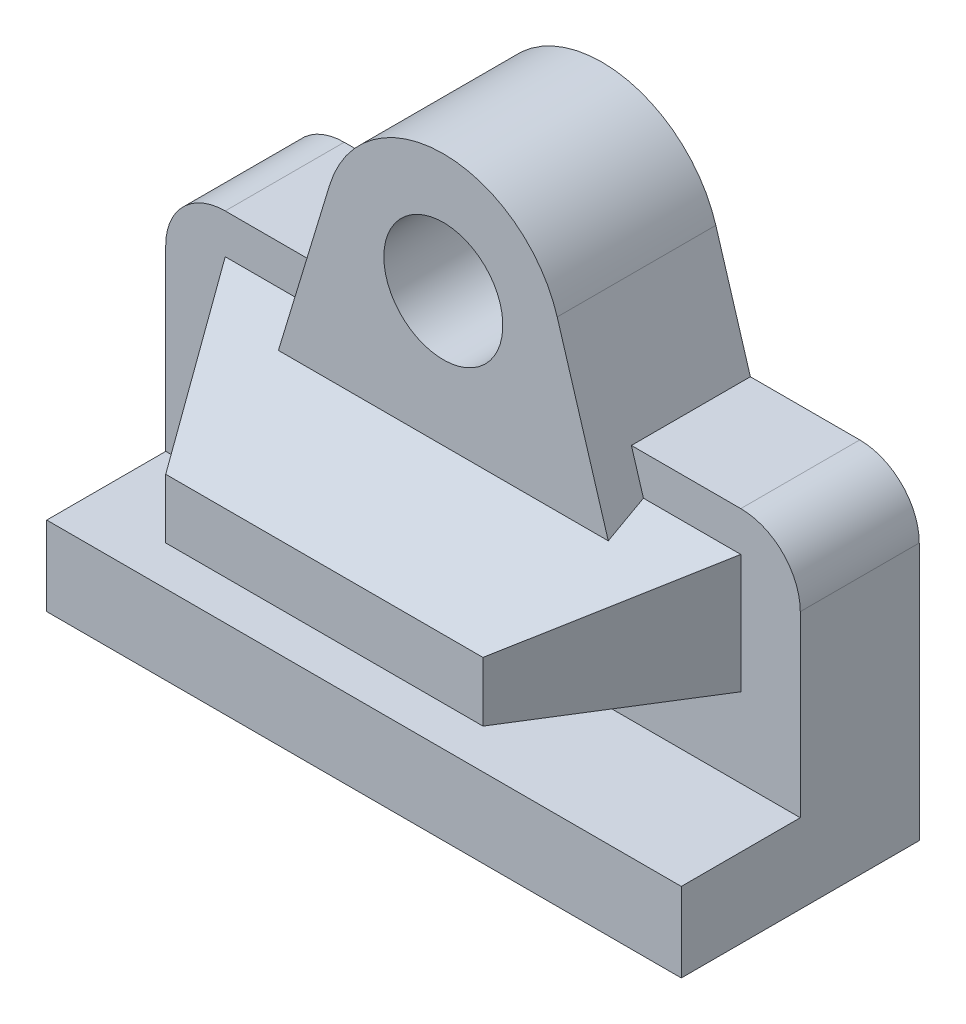
SolidWorks part; units mm, degrees
ref_plane "Front Plane" through (0, 0, 0) normal (0, 0, 1) x (1, 0, 0)
ref_plane "Top Plane" through (0, 0, 0) normal (0, 1, 0) x (1, 0, 0)
ref_plane "Right Plane" through (0, 0, 0) normal (1, 0, 0) x (0, 0, -1)
sketch "Sketch1" plane through (0, 0, 0) normal (0, 0, 1) x (1, 0, 0)
  line L0 (0, 0) -> (0, 63.5) construction
  line L1 (-50.8, 0) -> (50.8, 0)
  line L2 (50.8, 0) -> (50.8, 12.7)
  line L3 (50.8, 12.7) -> (-50.8, 12.7)
  line L4 (50.8, 12.7) -> (50.8, 41.275)
  line L5 (41.275, 50.8) -> (23.7595, 50.8)
  line L6 (-50.8, 25.4) -> (50.8, 25.4) construction
  line L7 (18.2298, 69.0298) -> (28.575, 34.925)
  line L8 (28.575, 34.925) -> (-28.575, 34.925)
  line L9 (0, 63.5) -> (0, 73.025) construction
  line L10 (-50.8, 0) -> (-50.8, 12.7)
  line L11 (-18.2298, 69.0298) -> (-28.575, 34.925)
  line L12 (-41.275, 50.8) -> (-23.7595, 50.8)
  line L13 (-50.8, 12.7) -> (-50.8, 41.275)
  arc A0 (50.8, 41.275) -> (41.275, 50.8) centre (41.275, 41.275) ccw
  circle A1 centre (0, 63.5) radius 9.525
  arc A2 (-50.8, 41.275) -> (-41.275, 50.8) centre (-41.275, 41.275) cw
  circle A3 centre (0, 63.5) radius 19.05
  point P6 (-50.8, 50.8)
  point P10 (50.8, 50.8)
  point P21 (0, 25.4)
  point P25 (0, 34.925)
  point P27 (0, 12.7)
  dimension "D4" = 9.525
  dimension "D5" = 19.05
  dimension "D10" = 38.1
  dimension "D1" = 50.8
  dimension "D2" = 12.7
  dimension "D3" = 38.1
  dimension "D6" = 12.7
  dimension "D7" = 38.1
  dimension "D8" = 28.575
  dimension "D9" = 34.925
extrude "Boss-Extrude1" add sketch "Sketch1" along normal blind 19.05 contours A3 A1 | A3 L11 L8 L7 | A2 L13 L3 L4 A0 L5 L7 L8 L11 L12 region at (0, 28.5216, 0) region at (0, 43.5132, 0) region at (0, 82.0112, 0)
extrude "Boss-Extrude2" add sketch "Sketch1<3>" along normal blind 25.4 contours A3 L11 L8 L7 | A3 A1 region at (0, 43.5132, 0) region at (0, 82.0112, 0)
sketch "Sketch1<3>" plane through (0, 0, 0) normal (0, 0, 1) x (1, 0, 0) same geometry as "Sketch1"
extrude "Boss-Extrude3" add sketch "Sketch1<4>" along normal blind 38.1 contours L10 L1 L2 L3 region at (0, 6.35, 0)
sketch "Sketch1<4>" plane through (0, 0, 0) normal (0, 0, 1) x (1, 0, 0) same geometry as "Sketch1"
sketch "Sketch2" plane through (0, 0, 19.05) normal (0, 0, 1) x (1, 0, 0)
  line L0 (0, 12.7) -> (0, 53.975) construction
  line L1 (50.8, 12.7) -> (-50.8, 12.7) construction
  line L2 (-41.275, 44.45) -> (41.275, 44.45)
  line L3 (50.8, 12.7) -> (-50.8, 12.7) construction
  line L4 (-41.275, 44.45) -> (-41.275, 25.4)
  line L5 (-41.275, 25.4) -> (41.275, 25.4)
  line L6 (41.275, 25.4) -> (41.275, 44.45)
  circle A0 centre (0, 63.5) radius 9.525 construction
  point P9 (0, 44.45)
  dimension "D1" = 31.75
  dimension "D2" = 19.05
  dimension "D3" = 82.55
ref_plane "Plane1" through (0, 0, 44.45) normal (0, 0, 1) x (1, 0, 0)
sketch "Sketch3" plane through (0, 0, 44.45) normal (0, 0, 1) x (1, 0, 0)
  line L0 (-41.275, 25.4) -> (41.275, 25.4) construction
  line L1 (-25.4, 25.4) -> (25.4, 25.4)
  line L2 (-25.4, 25.4) -> (-25.4, 34.925)
  line L3 (-25.4, 34.925) -> (25.4, 34.925)
  line L4 (25.4, 25.4) -> (25.4, 34.925)
  line L5 (0, 12.7) -> (0, 53.975) construction
  point P8 (0, 34.925)
  dimension "D1" = 25.4
  dimension "D2" = 9.525
loft "Loft1" add profiles "Sketch2", "Sketch3"
